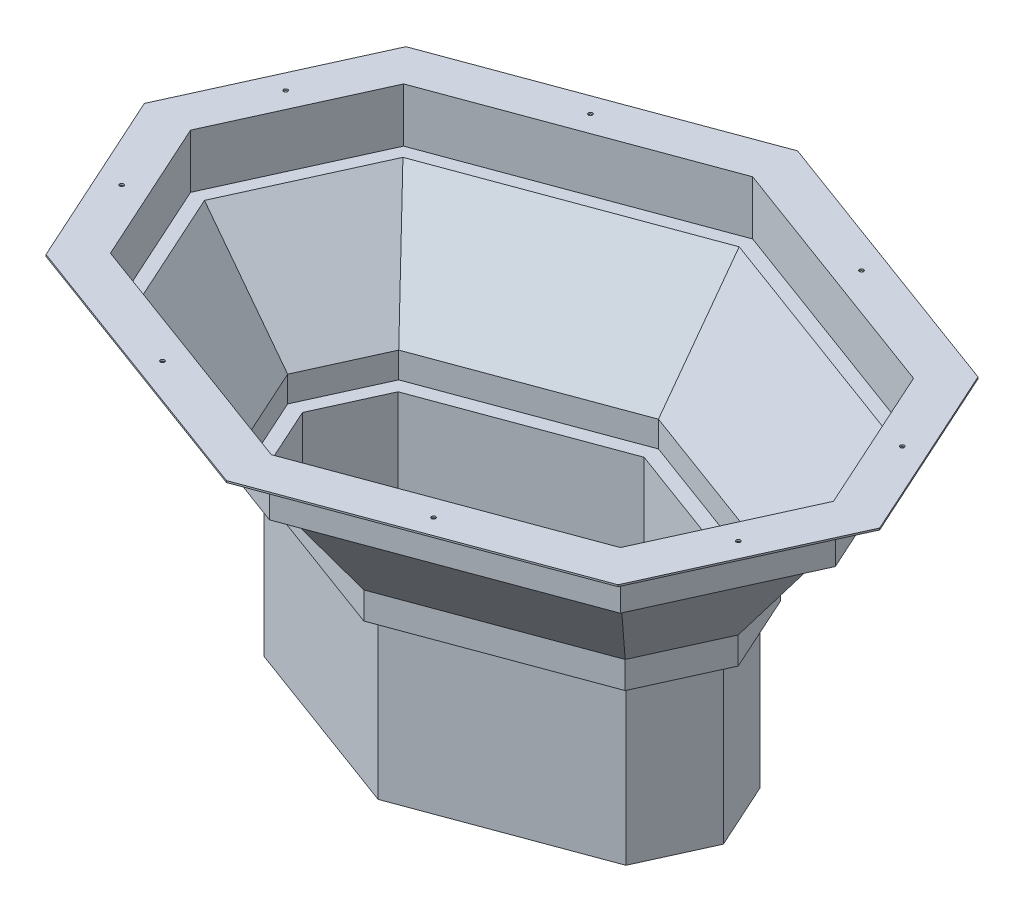
SolidWorks part; units mm, degrees
material "6061-T6 (SS)"
ref_plane "Front Plane" through (0, 0, 0) normal (0, 0, 1) x (1, 0, 0)
ref_plane "Top Plane" through (0, 0, 0) normal (0, 1, 0) x (1, 0, 0)
ref_plane "Right Plane" through (0, 0, 0) normal (1, 0, 0) x (0, 0, -1)
sketch "Sketch1" plane through (0, 0, 0) normal (0, 1, 0) x (1, 0, 0)
  line L0 (0, 0) -> (0, 457.2) construction
  line L1 (-609.6, 0) -> (-483.0506, 278.8894)
  line L2 (-609.6, 0) -> (0, 0) construction
  line L3 (483.0506, -278.8894) -> (-483.0506, -278.8894) construction
  line L4 (483.0506, -278.8894) -> (483.0506, 278.8894) construction
  line L5 (483.0506, 278.8894) -> (-483.0506, 278.8894) construction
  line L6 (-483.0506, -278.8894) -> (-483.0506, 278.8894) construction
  line L7 (483.0506, -278.8894) -> (-483.0506, 278.8894) construction
  line L8 (483.0506, 278.8894) -> (-483.0506, -278.8894) construction
  line L9 (-483.0506, 278.8894) -> (0, 457.2)
  line L10 (0, 457.2) -> (483.0506, 278.8894)
  line L11 (483.0506, 278.8894) -> (609.6, 0)
  line L12 (609.6, 0) -> (483.0506, -278.8894)
  line L13 (483.0506, -278.8894) -> (0, -457.2)
  line L14 (0, -457.2) -> (-483.0506, -278.8894)
  line L15 (-609.6, 0) -> (-483.0506, -278.8894)
  ellipse E0 centre (0, 0) end of major axis (-609.6, 0) minor radius 457.2 construction
  dimension "D1" = 609.6
  dimension "D2" = 457.2
  dimension "D3" = 30
extrude "Boss-Extrude1" add sketch "Sketch1" against normal blind 101.6
sketch "Sketch3" plane through (0, -101.6, 0) normal (0, -1, 0) x (1, 0, 0)
  line L0 (-464.3036, -258.7343) -> (0, -430.1247)
  line L1 (0, -430.1247) -> (464.3036, -258.7343)
  line L2 (464.3036, -258.7343) -> (581.7074, 0)
  line L3 (581.7074, 0) -> (464.3036, 258.7343)
  line L4 (464.3036, 258.7343) -> (0, 430.1247)
  line L5 (0, 430.1247) -> (-464.3036, 258.7343)
  line L6 (-464.3036, 258.7343) -> (-581.7074, 0)
  line L7 (-581.7074, 0) -> (-464.3036, -258.7343)
  line L8 (-483.0506, -278.8894) -> (0, -457.2)
  line L9 (0, -457.2) -> (483.0506, -278.8894)
  line L10 (483.0506, -278.8894) -> (609.6, 0)
  line L11 (609.6, 0) -> (483.0506, 278.8894)
  line L12 (483.0506, 278.8894) -> (0, 457.2)
  line L13 (0, 457.2) -> (-483.0506, 278.8894)
  line L14 (-483.0506, 278.8894) -> (-609.6, 0)
  line L15 (-609.6, 0) -> (-483.0506, -278.8894)
  line L16 (-483.0506, -278.8894) -> (0, -457.2) construction
  line L17 (0, -457.2) -> (483.0506, -278.8894) construction
  line L18 (483.0506, -278.8894) -> (609.6, 0) construction
  line L19 (609.6, 0) -> (483.0506, 278.8894) construction
  line L20 (483.0506, 278.8894) -> (0, 457.2) construction
  line L21 (0, 457.2) -> (-483.0506, 278.8894) construction
  line L22 (-483.0506, 278.8894) -> (-609.6, 0) construction
  line L23 (-609.6, 0) -> (-483.0506, -278.8894) construction
  dimension "D1" = 0
  dimension "D2" = 25.4
ref_plane "Plane1" through (0, -304.8, 0) normal (0, -1, 0) x (-1, 0, 0)
sketch "Sketch2" plane through (0, -304.8, 0) normal (0, -1, 0) x (-1, 0, 0)
  line L0 (0, 279.4925) -> (-360.0052, 146.6021)
  line L1 (-360.0052, 146.6021) -> (-426.5277, 0)
  line L2 (-426.5277, 0) -> (-360.0052, -146.6021)
  line L3 (-360.0052, -146.6021) -> (0, -279.4925)
  line L4 (0, -279.4925) -> (360.0052, -146.6021)
  line L5 (360.0052, -146.6021) -> (426.5277, 0)
  line L6 (426.5277, 0) -> (360.0052, 146.6021)
  line L7 (360.0052, 146.6021) -> (0, 279.4925)
  line L8 (483.0506, 278.8894) -> (0, 457.2)
  line L9 (609.6, 0) -> (483.0506, 278.8894)
  line L10 (483.0506, -278.8894) -> (609.6, 0)
  line L11 (0, -457.2) -> (483.0506, -278.8894)
  line L12 (-483.0506, -278.8894) -> (0, -457.2)
  line L13 (-609.6, 0) -> (-483.0506, -278.8894)
  line L14 (-483.0506, 278.8894) -> (-609.6, 0)
  line L15 (0, 457.2) -> (-483.0506, 278.8894)
  line L16 (483.0506, 278.8894) -> (0, 457.2) construction
  line L17 (609.6, 0) -> (483.0506, 278.8894) construction
  line L18 (483.0506, -278.8894) -> (609.6, 0) construction
  line L19 (0, -457.2) -> (483.0506, -278.8894) construction
  line L20 (-483.0506, -278.8894) -> (0, -457.2) construction
  line L21 (-609.6, 0) -> (-483.0506, -278.8894) construction
  line L22 (-483.0506, 278.8894) -> (-609.6, 0) construction
  line L23 (0, 457.2) -> (-483.0506, 278.8894) construction
  dimension "D2" = 177.7075
  dimension "D3" = 166.712
  dimension "D4" = 166.712
  dimension "D5" = 166.712
  dimension "D6" = 166.712
  dimension "D7" = 166.712
  dimension "D8" = 166.712
  dimension "D9" = 166.712
  dimension "D1" = 0
loft "Loft1" add profiles "Sketch3", "Sketch2" connector at (-464.3036, -101.6, 258.7343) connector at (-360.0052, -304.8, 146.6021)
sketch "Sketch4" plane through (0, -304.8, 0) normal (0, -1, 0) x (1, 0, 0)
  line L8 (0, -279.4925) -> (360.0052, -146.6021)
  line L9 (0, -279.4925) -> (360.0052, -146.6021)
  line L10 (360.0052, -146.6021) -> (426.5277, 0)
  line L11 (360.0052, -146.6021) -> (426.5277, 0)
  line L12 (426.5277, 0) -> (360.0052, 146.6021)
  line L13 (426.5277, 0) -> (360.0052, 146.6021)
  line L14 (360.0052, 146.6021) -> (0, 279.4925)
  line L15 (360.0052, 146.6021) -> (0, 279.4925)
  line L16 (0, 279.4925) -> (-360.0052, 146.6021)
  line L17 (0, 279.4925) -> (-360.0052, 146.6021)
  line L18 (-360.0052, 146.6021) -> (-426.5277, 0)
  line L19 (-360.0052, 146.6021) -> (-426.5277, 0)
  line L20 (-426.5277, 0) -> (-360.0052, -146.6021)
  line L21 (-426.5277, 0) -> (-360.0052, -146.6021)
  line L22 (-360.0052, -146.6021) -> (0, -279.4925)
  line L23 (-360.0052, -146.6021) -> (0, -279.4925)
  dimension "D1" = 0
extrude "Boss-Extrude2" add sketch "Sketch4" along normal blind 50.8
sketch "Sketch5" plane through (0, 0, 0) normal (0, 1, 0) x (1, 0, 0)
  line L0 (0, 538.4258) -> (-539.2916, 339.3547)
  line L1 (-539.2916, 339.3547) -> (-693.2779, 0)
  line L2 (-693.2779, 0) -> (-539.2916, -339.3547)
  line L3 (-539.2916, -339.3547) -> (0, -538.4258)
  line L4 (0, -538.4258) -> (539.2916, -339.3547)
  line L5 (539.2916, -339.3547) -> (693.2779, 0)
  line L6 (693.2779, 0) -> (539.2916, 339.3547)
  line L7 (539.2916, 339.3547) -> (0, 538.4258)
  line L8 (0, 457.2) -> (-483.0506, 278.8894)
  line L9 (-483.0506, 278.8894) -> (-609.6, 0)
  line L10 (-609.6, 0) -> (-483.0506, -278.8894)
  line L11 (-483.0506, -278.8894) -> (0, -457.2)
  line L12 (0, -457.2) -> (483.0506, -278.8894)
  line L13 (483.0506, -278.8894) -> (609.6, 0)
  line L14 (609.6, 0) -> (483.0506, 278.8894)
  line L15 (483.0506, 278.8894) -> (0, 457.2)
  line L16 (0, 457.2) -> (-483.0506, 278.8894) construction
  line L17 (-483.0506, 278.8894) -> (-609.6, 0) construction
  line L18 (-609.6, 0) -> (-483.0506, -278.8894) construction
  line L19 (-483.0506, -278.8894) -> (0, -457.2) construction
  line L20 (0, -457.2) -> (483.0506, -278.8894) construction
  line L21 (483.0506, -278.8894) -> (609.6, 0) construction
  line L22 (609.6, 0) -> (483.0506, 278.8894) construction
  line L23 (483.0506, 278.8894) -> (0, 457.2) construction
  dimension "D1" = 0
  dimension "D2" = 76.2
extrude "Boss-Extrude3" add sketch "Sketch5" along normal blind 3.175
sketch "Sketch6" plane through (0, -355.6, 0) normal (0, -1, 0) x (1, 0, 0)
  line L0 (0, 252.4172) -> (-341.2582, 126.447)
  line L1 (-341.2582, 126.447) -> (-398.6351, 0)
  line L2 (-398.6351, 0) -> (-341.2582, -126.447)
  line L3 (-341.2582, -126.447) -> (0, -252.4172)
  line L4 (0, -252.4172) -> (341.2582, -126.447)
  line L5 (341.2582, -126.447) -> (398.6351, 0)
  line L6 (398.6351, 0) -> (341.2582, 126.447)
  line L7 (341.2582, 126.447) -> (0, 252.4172)
  line L8 (360.0052, -146.6021) -> (426.5277, 0)
  line L9 (426.5277, 0) -> (360.0052, 146.6021)
  line L10 (360.0052, 146.6021) -> (0, 279.4925)
  line L11 (0, 279.4925) -> (-360.0052, 146.6021)
  line L12 (-360.0052, 146.6021) -> (-426.5277, 0)
  line L13 (-426.5277, 0) -> (-360.0052, -146.6021)
  line L14 (-360.0052, -146.6021) -> (0, -279.4925)
  line L15 (0, -279.4925) -> (360.0052, -146.6021)
  line L16 (360.0052, -146.6021) -> (426.5277, 0) construction
  line L17 (426.5277, 0) -> (360.0052, 146.6021) construction
  line L18 (360.0052, 146.6021) -> (0, 279.4925) construction
  line L19 (0, 279.4925) -> (-360.0052, 146.6021) construction
  line L20 (-360.0052, 146.6021) -> (-426.5277, 0) construction
  line L21 (-426.5277, 0) -> (-360.0052, -146.6021) construction
  line L22 (-360.0052, -146.6021) -> (0, -279.4925) construction
  line L23 (0, -279.4925) -> (360.0052, -146.6021) construction
  dimension "D1" = 0
  dimension "D2" = 25.4
extrude "Boss-Extrude4" add sketch "Sketch6" along normal blind 304.8
shell "Shell2" thickness 3.175 removed face at (0, 3.175, 0)
sketch "Sketch7" [suppressed] plane through (0, 0, 0) normal (0, 1, 0) x (1, 0, 0)
  line L0 (-357.6619, 144.0827) -> (0, 276.108) construction
  line L1 (-423.0411, 0) -> (-357.6619, 144.0827) construction
  line L2 (-357.6619, -144.0827) -> (-423.0411, 0) construction
  line L3 (-357.6619, -144.0827) -> (0, -276.108) construction
  line L4 (0, -276.108) -> (357.6619, -144.0827) construction
  line L5 (357.6619, -144.0827) -> (423.0411, 0) construction
  line L6 (357.6619, 144.0827) -> (423.0411, 0) construction
  line L7 (357.6619, 144.0827) -> (0, 276.108) construction
  line L8 (-357.6619, 144.0827) -> (0, 276.108) construction
  line L9 (-423.0411, 0) -> (-357.6619, 144.0827) construction
  line L10 (-357.6619, -144.0827) -> (-423.0411, 0) construction
  line L11 (-357.6619, -144.0827) -> (0, -276.108) construction
  line L12 (0, -276.108) -> (357.6619, -144.0827) construction
  line L13 (357.6619, -144.0827) -> (423.0411, 0) construction
  line L14 (357.6619, 144.0827) -> (423.0411, 0) construction
  line L15 (357.6619, 144.0827) -> (0, 276.108) construction
sketch "Sketch8" plane through (0, 3.175, 0) normal (0, 1, 0) x (1, 0, 0)
  line L0 (511.1711, 309.122) -> (0, 497.8129) construction
  line L1 (0, 497.8129) -> (-511.1711, 309.122) construction
  line L2 (-511.1711, 309.122) -> (-651.4389, 0) construction
  line L3 (-651.4389, 0) -> (-511.1711, -309.122) construction
  line L4 (-511.1711, -309.122) -> (0, -497.8129) construction
  line L5 (0, -497.8129) -> (511.1711, -309.122) construction
  line L6 (511.1711, -309.122) -> (651.4389, 0) construction
  line L7 (651.4389, 0) -> (511.1711, 309.122) construction
  line L8 (539.2916, 339.3547) -> (0, 538.4258)
  line L9 (0, 538.4258) -> (-539.2916, 339.3547)
  line L10 (-539.2916, 339.3547) -> (-693.2779, 0)
  line L11 (-693.2779, 0) -> (-539.2916, -339.3547)
  line L12 (-539.2916, -339.3547) -> (0, -538.4258)
  line L13 (0, -538.4258) -> (539.2916, -339.3547)
  line L14 (539.2916, -339.3547) -> (693.2779, 0)
  line L15 (693.2779, 0) -> (539.2916, 339.3547)
  line L16 (539.2916, 339.3547) -> (0, 538.4258) construction
  line L17 (0, 538.4258) -> (-539.2916, 339.3547) construction
  line L18 (-539.2916, 339.3547) -> (-693.2779, 0) construction
  line L19 (-693.2779, 0) -> (-539.2916, -339.3547) construction
  line L20 (-539.2916, -339.3547) -> (0, -538.4258) construction
  line L21 (0, -538.4258) -> (539.2916, -339.3547) construction
  line L22 (539.2916, -339.3547) -> (693.2779, 0) construction
  line L23 (693.2779, 0) -> (539.2916, 339.3547) construction
  circle A0 centre (-255.5855, 403.4675) radius 3.81
  circle A1 centre (255.5855, 403.4675) radius 3.81
  circle A2 centre (581.305, 154.561) radius 3.81
  circle A3 centre (581.305, -154.561) radius 3.81
  circle A4 centre (255.5855, -403.4675) radius 3.81
  circle A5 centre (-255.5855, -403.4675) radius 3.81
  circle A6 centre (-581.305, -154.561) radius 3.81
  circle A7 centre (-581.305, 154.561) radius 3.81
  dimension "D3" = 7.62
  dimension "D1" = 0
  dimension "D2" = 38.1
extrude "Cut-Extrude1" cut sketch "Sketch8" against normal up to next
sketch "Sketch9" plane through (0, -660.4, 0) normal (0, -1, 0) x (1, 0, 0)
  line L1 (1009.9465, -645.8443) -> (-874.8808, -645.8443)
  line L2 (1009.9465, -645.8443) -> (1009.9465, 608.3567)
  line L3 (1009.9465, 608.3567) -> (-874.8808, 608.3567)
  line L4 (-874.8808, -645.8443) -> (-874.8808, 608.3567)
extrude "Boss-Extrude5" [suppressed] add sketch "Sketch9" against normal blind 572.102 separate body
combine bodies "Combine1" [suppressed] operation type subtract main body 107 bodies to subtract 106
